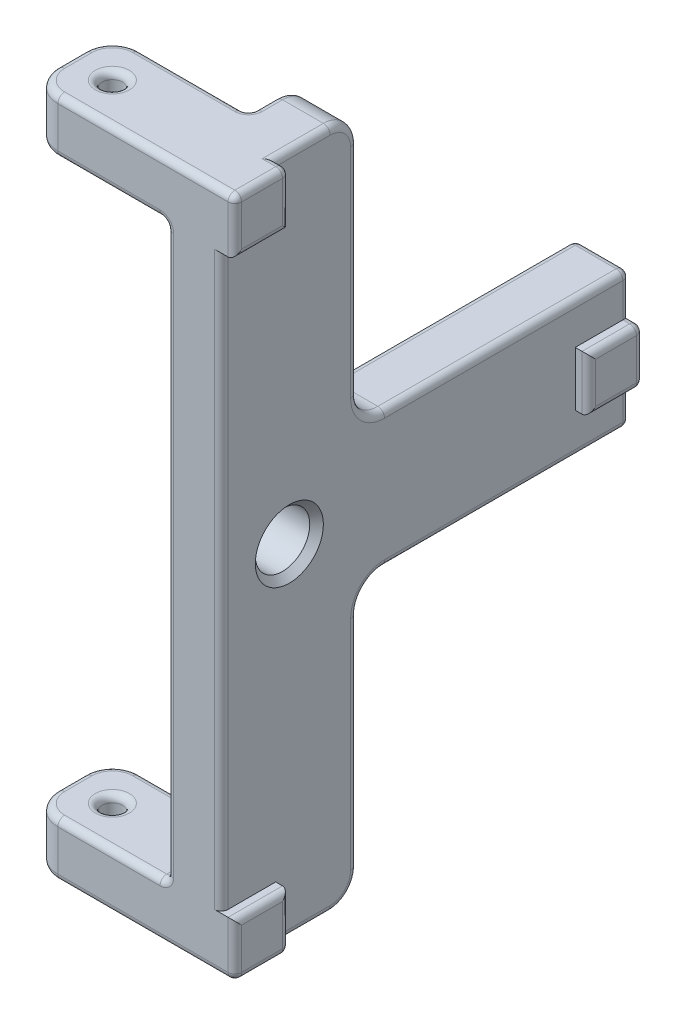
SolidWorks part; units mm, degrees
note: The reader was unsure of these and kept them because the rebuilt part matched: shared geometry of "Sketch2<3>", "Sketch2<4>".
material "6061 Alloy"
ref_plane "Front Plane" through (0, 0, 0) normal (0, 0, 1) x (1, 0, 0)
ref_plane "Top Plane" through (0, 0, 0) normal (0, 1, 0) x (1, 0, 0)
ref_plane "Right Plane" through (0, 0, 0) normal (1, 0, 0) x (0, 0, -1)
sketch "Sketch2" plane through (0, 0, 0) normal (1, 0, 0) x (0, 0, -1)
  line L0 (-25, 0) -> (5, 0) construction
  line L1 (-25, 25) -> (-15, 25)
  line L2 (-25, 25) -> (-25, -25)
  line L3 (-25, -25) -> (-15, -25)
  line L5 (-25, 25) -> (5, -5) construction
  line L6 (-25, -25) -> (5, 5) construction
  line L7 (-25, -21) -> (-19, -21)
  line L8 (-25, 25) -> (-19, 25)
  line L9 (-25, 25) -> (-25, 21)
  line L10 (-25, 21) -> (-19, 21)
  line L11 (-19, 25) -> (-19, 21)
  line L12 (-19, -25) -> (-19, -21)
  line L13 (-25, -25) -> (-19, -25)
  line L14 (-25, -25) -> (-25, -21)
  line L17 (-15, 25) -> (-15, 5)
  line L18 (-15, 5) -> (5, 5)
  line L19 (5, 5) -> (5, -5)
  line L20 (-15, -5) -> (5, -5)
  line L21 (-15, -25) -> (-15, -5)
  circle A1 centre (-20, 0) radius 2
  point P0 (0, 0)
  point P7 (0, 0)
  point P23 (5, 0)
  dimension "D4" = 4
  dimension "D1" = 50
  dimension "D2" = 20
  dimension "D5" = 5
  dimension "D6" = 25
  dimension "D7" = 6
  dimension "D8" = 4
  dimension "D9" = 10
  dimension "D10" = 25
  dimension "D11" = 20
extrude "Boss-Extrude1" add sketch "Sketch2" along normal blind 5
extrude "Boss-Extrude2" add sketch "Sketch2<3>" against normal blind 10 contours L11 L1 L2 L10 | L3 L12 L7 L2
sketch "Sketch2<3>" plane through (0, 0, 0) normal (1, 0, 0) x (0, 0, -1) same geometry as "Sketch2"
extrude "Cut-Extrude1" cut sketch "Sketch2<4>" along normal blind 10 contours A1
sketch "Sketch2<4>" plane through (0, 0, 0) normal (1, 0, 0) x (0, 0, -1) same geometry as "Sketch2"
fillet "Fillet1" radius 2 4 edges at (-10, -23, 19) (-10, -23, 25) (-10, 23, 19) (-10, 23, 25)
sketch "Sketch3" plane through (0, 25, 0) normal (0, 1, 0) x (1, 0, 0)
  line L0 (-10, -23) -> (-10, -21) construction
  line L1 (5, -25) -> (-8, -25) construction
  circle A0 centre (-7, -22) radius 0.75
  dimension "D1" = 1.5
  dimension "D3" = 3
  dimension "D2" = 3
extrude "Cut-Extrude3" cut sketch "Sketch3" against normal blind 50
sketch "Sketch4" plane through (5, 0, 0) normal (1, 0, 0) x (0, 0, -1)
  line L2 (-25, 25) -> (-15, 25) construction
  line L3 (-21, 25) -> (-15, 25)
  line L4 (-25, 25) -> (-25, -25) construction
  line L5 (-25, 21) -> (-25, -21)
  line L6 (-25, -25) -> (-15, -25) construction
  line L7 (-21, -25) -> (-15, -25)
  line L10 (-15, 25) -> (-15, 5) construction
  line L13 (-25, 21) -> (-21, 21)
  line L14 (-21, 25) -> (-21, 21)
  line L17 (-25, -21) -> (-21, -21)
  line L18 (-21, -25) -> (-21, -21)
  line L19 (1, 2) -> (5, 2)
  line L20 (1, 2) -> (1, -2)
  line L21 (1, -2) -> (5, -2)
  line L22 (5, 2) -> (5, -2)
  line L23 (-15, 25) -> (-15, 5)
  line L24 (-15, 5) -> (5, 5) construction
  line L25 (-15, 5) -> (5, 5)
  line L26 (-15, -5) -> (5, -5) construction
  line L27 (-15, -5) -> (5, -5)
  line L28 (-15, -25) -> (-15, -5) construction
  line L29 (-15, -25) -> (-15, -5)
  line L30 (5, 5) -> (5, -5) construction
  line L31 (5, 5) -> (5, -5)
  dimension "D1" = 4
  dimension "D2" = 4
  dimension "D3" = 4
  dimension "D4" = 4
  dimension "D5" = 4
  dimension "D6" = 4
  dimension "D7" = 2
  dimension "D8" = 5
extrude "Cut-Extrude4" cut sketch "Sketch4" against normal blind 1
fillet "Fillet4" radius 2 4 edges at (2, 25, 15) (2, -25, 15) (2, -5, 15) (2, 5, 15)
fillet "Fillet5" radius 0.5 60 edges at (-7, 21, 21.25) (-7, -25, 22.75) (-7, -21, 21.25) (-7, 25, 22.75) (5, 0, -5) (5, -25, 23) (2, 5, -5) (2, -5, -5) (4, -3.5, -5) (4.5, -2, -5) (4, -25, 19) (4.5, -25, 21) (4, 0, 25) (4.5, 25, 21) (4, 5, 4) (4, 3.5, -5) (4.5, 2, -5) (0, 0, -5) (4, 25, 19) (0, 15, 15) (0, 5, 4) (0, -5, 4) (0, -15, 15) (0, -24.4142, 15.5858) (0, 24.4142, 15.5858) (4, 15, 15) (4, -15, 15) (4, -5, 4) (4, -24.4142, 15.5858) (4, 24.4142, 15.5858) (0, -5.5858, 14.4142) (4, -5.5858, 14.4142) (0, 5.5858, 14.4142) (4, 5.5858, 14.4142) (-1.5, -25, 25) (-1.5, 25, 25) (0, 0, 25) (0, 25, 18) (0, 23, 19) (0, 21, 22) (5, 25, 23) (0, -25, 18) (0, -21, 22) (0, -23, 19) (-4, -25, 19) (-4, -21, 19) (-10, -21, 22) (-9.4142, -21, 24.4142) (-9.4142, -21, 19.5858) (-10, -25, 22) (-9.4142, -25, 24.4142) (-9.4142, -25, 19.5858) (-10, 21, 22) (-10, 25, 22) (-4, 21, 19) (-9.4142, 21, 24.4142) (-9.4142, 21, 19.5858) (-4, 25, 19) (-9.4142, 25, 24.4142) (-9.4142, 25, 19.5858)
fillet "Fillet7" radius 0.5 15 edges at (5, -22.75, 25) (5, -2, -2.75) (5, 21, 23) (5, 0, -1) (5, 2, -2.75) (5, -21, 23) (5, 22.75, 25) (5, -22.75, 21) (5, 22.75, 21) (4.8536, 1.8536, -4.8536) (4.8536, -1.8536, -4.8536) (4.8536, 24.8536, 21.1464) (4.8536, -24.8536, 21.1464) (4.8536, 24.8536, 24.8536) (4.8536, -24.8536, 24.8536)
chamfer "Chamfer1" distance 0.5 angle 45 1 edges at (4, 0, 18)
